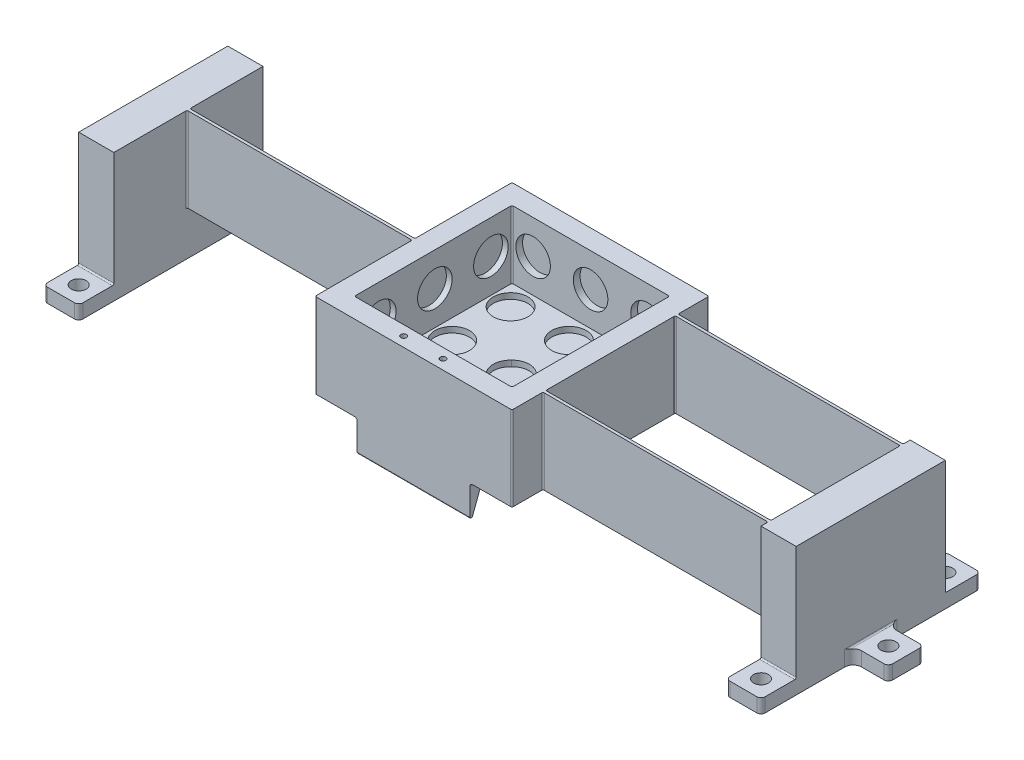
SolidWorks part; units mm, degrees
ref_plane "Front Plane" through (0, 0, 0) normal (0, 0, 1) x (1, 0, 0)
ref_plane "Top Plane" through (0, 0, 0) normal (0, 1, 0) x (1, 0, 0)
ref_plane "Right Plane" through (0, 0, 0) normal (1, 0, 0) x (0, 0, -1)
sketch "Sketch1" plane through (0, 0, 0) normal (0, 1, 0) x (1, 0, 0)
  line L1 (-35, -35) -> (35, -35)
  line L2 (-35, -35) -> (-35, 35)
  line L3 (-35, 35) -> (35, 35)
  line L4 (35, -35) -> (35, 35)
  line L5 (-35, -35) -> (35, 35) construction
  line L6 (-35, 35) -> (35, -35) construction
  point P0 (0, 0)
  dimension "D1" = 70
  dimension "D2" = 70
extrude "Boss-Extrude1" add sketch "Sketch1" along normal blind 30
shell "Shell1" thickness 7 removed face at (0, 30, 0)
sketch "Sketch2" plane through (0, 30, 0) normal (0, 1, 0) x (1, 0, 0)
  line L0 (-35, 35) -> (-35, -35) construction
  line L1 (-28, -28) -> (28, -28) construction
  line L2 (-28, -28) -> (-28, 28) construction
  line L3 (-28, 28) -> (28, 28) construction
  line L4 (28, -28) -> (28, 28) construction
  line L5 (-28, -28) -> (28, 28) construction
  line L6 (-28, 28) -> (28, -28) construction
  line L7 (35, 35) -> (-35, 35) construction
  point P0 (0, 0)
  dimension "D1" = 7
  dimension "D2" = 7
sketch "Sketch3" plane through (35, 0, 0) normal (1, 0, 0) x (0, 0, -1)
  line L0 (-35, 30) -> (35, 30) construction
  line L1 (-24, 30) -> (-23, 30)
  line L2 (-24, 30) -> (-24, 0)
  line L3 (-24, 0) -> (-23, 0)
  line L4 (-23, 30) -> (-23, 0)
  line L5 (-35, 0) -> (35, 0) construction
  line L6 (-28, 30) -> (28, 30) construction
  line L7 (-0.5, 30) -> (0.5, 30)
  line L8 (-0.5, 30) -> (-0.5, 0)
  line L9 (-0.5, 0) -> (0.5, 0)
  line L10 (0.5, 30) -> (0.5, 0)
  line L11 (28, 30) -> (-28, 30) construction
  line L12 (24, 30) -> (23, 30)
  line L13 (24, 30) -> (24, 0)
  line L14 (24, 0) -> (23, 0)
  line L15 (23, 30) -> (23, 0)
  line L16 (-23.5, 30) -> (-23.5, 0) construction
  line L17 (0, 30) -> (0, 0) construction
  line L18 (23.5, 0) -> (23.5, 30) construction
  dimension "D1" = 23
  dimension "D2" = 23
  dimension "D3" = 1
extrude "Boss-Extrude2" add sketch "Sketch3" along normal blind 80
sketch "Sketch5" plane through (115, 0, 0) normal (1, 0, 0) x (0, 0, -1)
  line L0 (-24, 30) -> (-24, 0) construction
  line L1 (-26.5, 30) -> (26.5, 30)
  line L2 (-26.5, 30) -> (-26.5, 0)
  line L3 (-26.5, 0) -> (26.5, 0)
  line L4 (26.5, 30) -> (26.5, 0)
  line L5 (28, 30) -> (-28, 30) construction
  line L6 (24, 0) -> (35, 0) construction
  line L7 (24, 0) -> (24, 30) construction
  dimension "D1" = 2.5
  dimension "D2" = 2.5
extrude "Boss-Extrude3" add sketch "Sketch5" along normal blind 12.5
sketch "Sketch6" plane through (0, 0, 0) normal (0, -1, 0) x (1, 0, 0)
  line L1 (115, 26.5) -> (127.5, 26.5)
  line L2 (115, 26.5) -> (115, -26.5)
  line L3 (115, -26.5) -> (127.5, -26.5)
  line L4 (127.5, 26.5) -> (127.5, -26.5)
extrude "Boss-Extrude4" add sketch "Sketch6" along normal blind 15.75
sketch "Sketch8" plane through (0, -15.75, 0) normal (0, -1, 0) x (1, 0, 0)
  line L1 (127.5, -26.5) -> (115, -26.5)
  line L2 (127.5, -26.5) -> (127.5, -39)
  line L3 (127.5, -39) -> (115, -39)
  line L4 (115, -26.5) -> (115, -39)
  line L5 (127.5, 26.5) -> (115, 26.5)
  line L6 (127.5, 26.5) -> (127.5, 39)
  line L7 (127.5, 39) -> (115, 39)
  line L8 (115, 26.5) -> (115, 39)
  line L13 (127.5, -26.5) -> (127.5, 26.5) construction
  line L14 (140, -6.25) -> (127.5, -6.25)
  line L15 (140, -6.25) -> (140, 6.25)
  line L16 (140, 6.25) -> (127.5, 6.25)
  line L17 (127.5, -6.25) -> (127.5, 6.25)
  line L18 (140, -6.25) -> (127.5, 6.25) construction
  line L19 (140, 6.25) -> (127.5, -6.25) construction
  line L20 (115, 0) -> (140, 0) construction
  line L21 (115, 0.5) -> (115, -0.5) construction
  point P13 (133.75, 0)
  point P19 (127.5, 0)
  point P20 (127.5, 0)
extrude "Boss-Extrude5" add sketch "Sketch8" against normal blind 5
hole_wizard "Ø5.0mm Dowel Hole1" positions "Sketch9" profile "Sketch10" hole size "Ø5.0" standard "ANSI Metric"
sketch "Sketch9" plane through (0, -10.75, 0) normal (0, 1, 0) x (1, 0, 0)
  line L0 (121.25, 39) -> (121.25, 32.75) construction
  line L1 (115, 39) -> (127.5, 39) construction
  line L2 (121.25, 32.75) -> (127.5, 32.75) construction
  line L3 (127.5, 39) -> (127.5, 26.5) construction
  line L5 (127.5, 0) -> (133.75, 0) construction
  line L6 (127.5, -6.25) -> (127.5, 6.25) construction
  line L7 (133.75, 0) -> (133.75, 6.25) construction
  line L8 (127.5, 6.25) -> (140, 6.25) construction
  line L10 (121.25, -26.5) -> (121.25, -32.75) construction
  line L11 (115, -26.5) -> (127.5, -26.5) construction
  line L12 (121.25, -32.75) -> (127.5, -32.75) construction
  line L13 (127.5, -26.5) -> (127.5, -39) construction
  point P0 (121.25, 32.75)
  point P2 (133.75, 0)
  point P4 (121.25, -32.75)
sketch "Sketch10" plane through (121.25, -10.75, -32.75) normal (1, 0, 0) x (0, 0, 1)
  line L0 (0, 0) -> (0, 18.1023)
  line L1 (0, 18.1023) -> (2.65, 16.51)
  line L2 (2.65, 16.51) -> (2.65, 0)
  line L5 (2.65, 0) -> (0, 0)
  line L10 (0, 18.1023) -> (-2.65, 16.51) construction
  line L11 (0, -6.35) -> (0, 107.95) construction
  dimension "Hole Dia." = 5.3
  dimension "Hole Depth" = 16.51
  dimension "Drill Angle" = 118
mirror "Mirror1" about plane through (0, 0, 0) normal (1, 0, 0) of "Boss-Extrude2", "Boss-Extrude3", "Boss-Extrude5", "Boss-Extrude4", "Ø5.0mm Dowel Hole1"
sketch "Sketch25" plane through (0, 30, 0) normal (0, 1, 0) x (1, 0, 0)
  line L1 (-115, 24) -> (-35, 24)
  line L2 (-115, 24) -> (-115, 23)
  line L3 (-115, 23) -> (-35, 23)
  line L4 (-35, 24) -> (-35, 23)
  line L5 (-115, -23) -> (-35, -23)
  line L6 (-115, -23) -> (-115, -24)
  line L7 (-115, -24) -> (-35, -24)
  line L8 (-35, -23) -> (-35, -24)
extrude "Cut-Extrude7" cut sketch "Sketch25" against normal through all both and the other way through all
fillet "Fillet2" radius 1.5 12 edges at (140, -13.25, 6.25) (140, -13.25, -6.25) (127.5, -13.25, -39) (115, -13.25, -39) (127.5, -13.25, 39) (115, -13.25, 39) (-115, -13.25, -39) (-127.5, -13.25, -39) (-140, -13.25, -6.25) (-140, -13.25, 6.25) (-115, -13.25, 39) (-127.5, -13.25, 39)
sketch "Sketch11" plane through (0, 6, 0) normal (0, 1, 0) x (1, 0, 0)
  line L26 (-28, -28) -> (-28, 28) construction
  line L32 (-28, -28) -> (28, -28) construction
  circle A0 centre (-21, -21) radius 6.15
  dimension "D1" = 12.3
  dimension "D2" = 0.85
  dimension "D3" = 0.85
extrude "Cut-Extrude1" cut sketch "Sketch11" against normal blind 2.05
pattern_linear "LPattern1" count 3 spacing 20.75 along (1, 0, 0) count 3 spacing 20.75 along (0, 0, -1) of "Cut-Extrude1"
sketch "Sketch14" plane through (0, 6, 0) normal (0, 1, 0) x (1, 0, 0)
  line L0 (-28, 0) -> (0, 0) construction
  line L1 (-28, 28) -> (-28, -28) construction
  line L2 (0, 0) -> (0, -28) construction
  line L3 (-28, -28) -> (28, -28) construction
  circle A0 centre (0, 0) radius 6.15
  dimension "D1" = 12.3
extrude "Cut-Extrude4" cut sketch "Sketch14" against normal blind 2.05
sketch "Sketch12" plane through (-28, 0, 0) normal (1, 0, 0) x (0, 0, -1)
  line L5 (-28, 18) -> (-19.35, 18) construction
  line L6 (-28, 30) -> (-28, 6) construction
  circle A0 centre (-19.35, 18) radius 6.15
  dimension "D1" = 12.3
  dimension "D2" = 2.5
extrude "Cut-Extrude2" cut sketch "Sketch12" against normal blind 2.05
pattern_linear "LPattern2" count 3 spacing 19.925 along (0, 0, -1) of "Cut-Extrude2"
sketch "Sketch13" plane through (0, 0, -28) normal (0, 0, -1) x (-1, 0, 0)
  line L6 (-28, 30) -> (-28, 6) construction
  line L7 (-20.35, 18) -> (-28, 18) construction
  circle A0 centre (-20.35, 18) radius 6.15
  dimension "D1" = 12.3
  dimension "D3" = 1.5
extrude "Cut-Extrude3" cut sketch "Sketch13" along normal blind 2.4
pattern_linear "LPattern3" count 3 spacing 20.425 along (-1, 0, 0) of "Cut-Extrude3"
mirror "Mirror2" about plane through (0, 0, 0) normal (1, 0, 0) of "LPattern2", "Cut-Extrude2"
sketch "Sketch24" plane through (0, 30, 0) normal (0, 1, 0) x (1, 0, 0)
  line L1 (35, 0.5) -> (115, 0.5)
  line L2 (35, 0.5) -> (35, -0.5)
  line L3 (35, -0.5) -> (115, -0.5)
  line L4 (115, 0.5) -> (115, -0.5)
extrude "Cut-Extrude6" cut sketch "Sketch24" against normal through all both and the other way through all
fillet "Fillet4" radius 0.5 4 edges at (-35, 15, 35) (35, 15, 35) (-35, 15, -35) (35, 15, -35)
sketch "Sketch19" plane through (0, 0, 0) normal (1, 0, 0) x (0, 0, -1)
  line L0 (-30, 0) -> (-35, -13.25)
  line L1 (-35, -13.25) -> (-35, 0)
  line L2 (-35, 0) -> (-30, 0)
  line L3 (0, 0) -> (-30, 0) construction
  line L4 (37.5, -15.75) -> (-37.5, -15.75) construction
  dimension "D1" = 5
  dimension "D2" = 30
  dimension "D3" = 2.5
extrude "Boss-Extrude8" add sketch "Sketch19" along normal mid plane 40
sketch "Sketch20" plane through (0, 0, 0) normal (1, 0, 0) x (0, 0, -1)
  line L0 (-35, 20) -> (-42.5, 20)
  line L1 (-42.5, 20) -> (-42.5, 30)
  line L2 (-26.5, 30) -> (-42.5, 30) construction
  line L5 (-42.5, 30) -> (-40, 30)
  line L6 (-40, 30) -> (-40, 22.5)
  line L7 (-40, 22.5) -> (-35, 22.5)
  line L8 (-35, 22.5) -> (-35, 20)
  line L9 (-35, 30) -> (-35, 0) construction
  line L10 (-35, 0) -> (-35, 30) construction
  dimension "D1" = 5
  dimension "D2" = 10
  dimension "D3" = 2.5
  dimension "D4" = 2.5
extrude "Place For Sensor" [suppressed] add sketch "Sketch20" along normal mid plane 10
fillet "Place For Sensor Fillet5" [suppressed] radius 0.5
fillet "Place For Sensor Fillet6" [suppressed] radius 1.5
hole_wizard "Place For Sensor Ø3.0mm Dowel Hole2" [suppressed] positions "Sketch21" profile "Sketch22" hole size "Ø3.0" standard "ANSI Metric"
sketch "Sketch21" [suppressed] plane through (0, 0, 32.5) normal (0, 0, 1) x (1, 0, 0)
  line L0 (-2.5, 27.5) -> (2.5, 27.5) construction
  line L2 (-18, 30) -> (18, 30) construction
  line L3 (-5, 28.5) -> (-5, 20.5) construction
  line L4 (5, 28.5) -> (5, 20.5) construction
  point P0 (-2.5, 27.5)
  point P2 (2.5, 27.5)
  dimension "D1" = 2.5
  dimension "D2" = 2.5
  dimension "D3" = 2.5
sketch "Sketch22" plane through (-2.5, 27.5, 32.5) normal (1, 0, 0) x (0, -1, 0)
  line L0 (0, 0) -> (0, 2.5)
  line L1 (0, 2.5) -> (1.65, 2.5)
  line L2 (1.65, 2.5) -> (1.65, 0)
  line L5 (1.65, 0) -> (0, 0)
  line L11 (0, -6.35) -> (0, 107.95) construction
  dimension "Thru Hole Dia." = 3.3
  dimension "Thru Hole Depth" = 2.5
sketch "Sketch23" plane through (0, 30, 0) normal (0, 1, 0) x (1, 0, 0)
  line L1 (-28, -28) -> (28, -28) construction
  circle A0 centre (-7, -31.5) radius 1
  circle A1 centre (7, -31.5) radius 1
  dimension "D4" = 2
  dimension "D1" = 3.5
  dimension "D2" = 14
  dimension "D3" = 7
extrude "Cut-Extrude5" cut sketch "Sketch23" against normal blind 6
fillet "Fillet3" radius 0.5 4 edges at (28, 18, -28) (-28, 18, -28) (28, 18, 28) (-28, 18, 28)
fillet "Fillet1" radius 0.5 16 edges at (121.25, -10.75, -26.5) (121.25, -10.75, 26.5) (-115, 15, 0.5) (-115, 15, -0.5) (-35, 15, 0.5) (-35, 15, -0.5) (-121.25, -10.75, -26.5) (-121.25, -10.75, 26.5) (35, 15, 24) (35, 15, 23) (115, 15, 24) (115, 15, 23) (35, 15, -24) (35, 15, -23) (115, 15, -24) (115, 15, -23)
fillet "Fillet5" radius 0.5 1 edges at (0, -13.25, 35)
fillet "Fillet6" radius 1 3 edges at (-20, 0, 32.5) (20, 0, 32.5) (0, 0, 30)
fillet "Fillet8" radius 3 4 edges at (127.5, -13, 6.25) (127.5, -13, -6.25) (-127.5, -13, -6.25) (-127.5, -13, 6.25)
